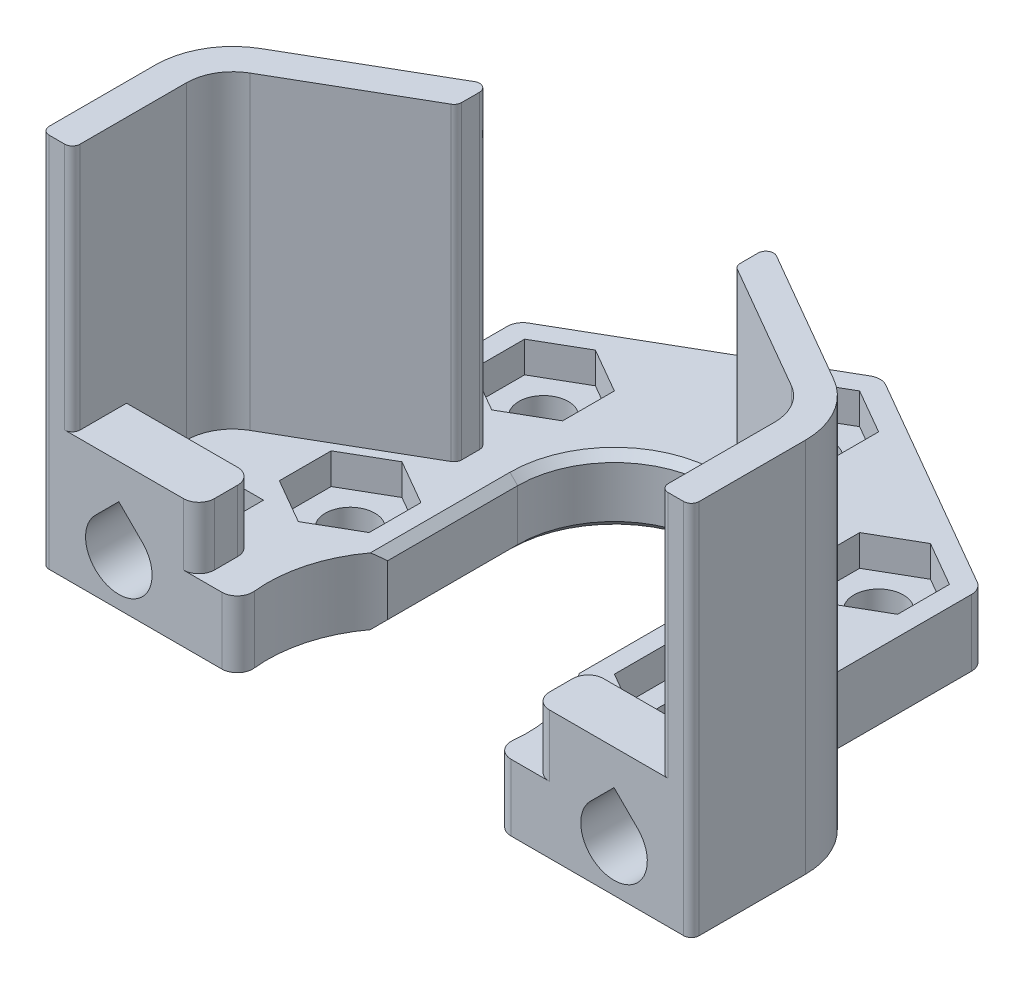
SolidWorks part; units mm, degrees
ref_plane "Front Plane" through (0, 0, 0) normal (0, 0, 1) x (1, 0, 0)
ref_plane "Top Plane" through (0, 0, 0) normal (0, 1, 0) x (1, 0, 0)
ref_plane "Right Plane" through (0, 0, 0) normal (1, 0, 0) x (0, 0, -1)
sketch "Sketch1" plane through (0, 0, 0) normal (0, 1, 0) x (1, 0, 0)
  line L0 (0, 0) -> (0, -54.0828) construction
  line L1 (0, 17.3205) -> (-15, 8.6603)
  line L2 (-15, 8.6603) -> (-15, -8.6603)
  line L3 (-15, -8.6603) -> (-6.25, -13.7121)
  line L4 (6.25, -13.7121) -> (15, -8.6603)
  line L5 (15, -8.6603) -> (15, 8.6603)
  line L6 (15, 8.6603) -> (0, 17.3205)
  line L7 (0, -54.6431) -> (0, 54.6431) construction
  line L8 (6.25, 0) -> (6.25, -13.7121)
  line L9 (-6.25, 0) -> (-6.25, -13.7121)
  line L11 (0, 12.5) -> (-10.8253, 6.25) construction
  line L12 (-10.8253, 6.25) -> (-10.8253, -6.25) construction
  line L13 (-10.8253, -6.25) -> (0, -12.5) construction
  line L14 (0, -12.5) -> (10.8253, -6.25) construction
  line L15 (10.8253, -6.25) -> (10.8253, 6.25) construction
  line L16 (10.8253, 6.25) -> (0, 12.5) construction
  circle A0 centre (0, 0) radius 15 construction
  arc A1 (6.25, 0) -> (-6.25, 0) centre (0, 0) ccw
  circle A2 centre (0, 0) radius 10.8253 construction
  circle A3 centre (0, 12.5) radius 1.6
  circle A4 centre (10.8253, 6.25) radius 1.6
  circle A5 centre (10.8253, -6.25) radius 1.6
  circle A6 centre (-10.8253, -6.25) radius 1.6
  circle A7 centre (-10.8253, 6.25) radius 1.6
  point P1 (0, -27.0414)
  dimension "D4" = 3.2
  dimension "D1" = 12.5
  dimension "D2" = 30
  dimension "D3" = 25
extrude "Boss-Extrude1" add sketch "Sketch1" along normal blind 4.3
fillet "Fillet1" radius 1 7 edges at (15, 2.15, -8.6603) (0, 2.15, -17.3205) (-15, 2.15, -8.6603) (-6.25, 2.15, 13.7121) (6.25, 2.15, 13.7121) (15, 2.15, 8.6603) (-15, 2.15, 8.6603)
sketch "Sketch2" plane through (0, 4.3, 0) normal (0, 1, 0) x (1, 0, 0)
  line L1 (0, 15.8486) -> (-2.9, 14.1743)
  line L2 (-2.9, 14.1743) -> (-2.9, 10.8257)
  line L3 (-2.9, 10.8257) -> (0, 9.1514)
  line L4 (0, 9.1514) -> (2.9, 10.8257)
  line L5 (2.9, 10.8257) -> (2.9, 14.1743)
  line L6 (2.9, 14.1743) -> (0, 15.8486)
  line L7 (13.7253, 4.5757) -> (13.7253, 7.9243)
  line L8 (13.7253, 7.9243) -> (10.8253, 9.5986)
  line L9 (10.8253, 9.5986) -> (7.9253, 7.9243)
  line L10 (7.9253, 7.9243) -> (7.9253, 4.5757)
  line L11 (7.9253, 4.5757) -> (10.8253, 2.9014)
  line L12 (10.8253, 2.9014) -> (13.7253, 4.5757)
  line L13 (13.7253, -4.5757) -> (10.8253, -2.9014)
  line L14 (10.8253, -2.9014) -> (7.9253, -4.5757)
  line L15 (7.9253, -4.5757) -> (7.9253, -7.9243)
  line L16 (7.9253, -7.9243) -> (10.8253, -9.5986)
  line L17 (10.8253, -9.5986) -> (13.7253, -7.9243)
  line L18 (13.7253, -7.9243) -> (13.7253, -4.5757)
  line L19 (-13.7253, -4.5757) -> (-13.7253, -7.9243)
  line L20 (-13.7253, -7.9243) -> (-10.8253, -9.5986)
  line L21 (-10.8253, -9.5986) -> (-7.9253, -7.9243)
  line L22 (-7.9253, -7.9243) -> (-7.9253, -4.5757)
  line L23 (-7.9253, -4.5757) -> (-10.8253, -2.9014)
  line L24 (-10.8253, -2.9014) -> (-13.7253, -4.5757)
  line L25 (-13.7253, 7.9243) -> (-13.7253, 4.5757)
  line L26 (-13.7253, 4.5757) -> (-10.8253, 2.9014)
  line L27 (-10.8253, 2.9014) -> (-7.9253, 4.5757)
  line L28 (-7.9253, 4.5757) -> (-7.9253, 7.9243)
  line L29 (-7.9253, 7.9243) -> (-10.8253, 9.5986)
  line L30 (-10.8253, 9.5986) -> (-13.7253, 7.9243)
  circle A0 centre (0, 12.5) radius 2.9 construction
  circle A1 centre (10.8253, 6.25) radius 2.9 construction
  circle A2 centre (10.8253, -6.25) radius 2.9 construction
  circle A3 centre (-10.8253, -6.25) radius 2.9 construction
  circle A4 centre (-10.8253, 6.25) radius 2.9 construction
  dimension "D1" = 5.8
extrude "Cut-Extrude1" cut sketch "Sketch2" against normal blind 2
sketch "Sketch3" plane through (0, 4.3, 0) normal (0, 1, 0) x (1, 0, 0)
  line L0 (0, 0) -> (0, -38.427) construction
  line L1 (-15, -8.0829) -> (-6.25, -11.98)
  line L2 (-20, -10.9697) -> (-20, -22.3767)
  line L3 (-18.3541, -24.0226) -> (18.3541, -24.0226)
  line L4 (20, -10.9697) -> (20, -22.3767)
  line L5 (0, -54.6431) -> (0, 54.6431) construction
  line L6 (15, -8.0829) -> (20, -10.9697)
  line L7 (-15, -8.0829) -> (-20, -10.9697)
  line L8 (-6.25, -11.98) -> (6.25, -11.98)
  line L9 (6.25, -11.98) -> (15, -8.0829)
  line L10 (-0.5, 17.0318) -> (-14.5, 8.9489) construction
  line L11 (14.5, 8.9489) -> (0.5, 17.0318) construction
  circle A0 centre (0, -14.0226) radius 10 construction
  arc A3 (20, -22.3767) -> (18.3541, -24.0226) centre (18.3541, -22.3767) cw
  arc A4 (-20, -22.3767) -> (-18.3541, -24.0226) centre (-18.3541, -22.3767) ccw
  point P31 (20, -24.0226)
  point P34 (-20, -24.0226)
  dimension "D1" = 20
  dimension "D2" = 40
extrude "Boss-Extrude2" add sketch "Sketch3" against normal up to surface (4.3 mm away) up to face at (-10.8253, 0, 7.85)
sketch "Sketch4" plane through (0, 4.3, 0) normal (0, 1, 0) x (1, 0, 0)
  line L0 (0, -54.6431) -> (0, 54.6431) construction
  circle A0 centre (0, -14.0226) radius 10 construction
  circle A1 centre (0, -14.0226) radius 8.4
  dimension "D1" = 20
  dimension "D2" = 16.8
extrude "Cut-Extrude2" cut sketch "Sketch4" against normal through all
sketch "Sketch5" plane through (0, 4.3, 0) normal (0, 1, 0) x (1, 0, 0)
  line L0 (-20, -10.9697) -> (-20, -22.3767) construction
  line L1 (-20, -16.0226) -> (20, -16.0226)
  line L2 (-20, -16.0226) -> (-20, -24.0226)
  line L3 (-20, -24.0226) -> (20, -24.0226)
  line L4 (20, -16.0226) -> (20, -24.0226)
  line L5 (-18.3541, -24.0226) -> (18.3541, -24.0226) construction
  line L6 (20, -22.3767) -> (20, -10.9697) construction
  point P0 (0, -16.0226)
  dimension "D1" = 8
extrude "Cut-Extrude3" cut sketch "Sketch5" against normal through all
other "Move Face1" face at (17.5, 2.15, 9.5263) face at (-17.5, 2.15, 9.5263) offset 5 parameters "D1"=5
sketch "Sketch6" plane through (0, 4.3, 0) normal (0, 1, 0) x (1, 0, 0)
  line L0 (-20, -12.5226) -> (-8.265, -12.5226)
  line L1 (8.265, -12.5226) -> (20, -12.5226)
  line L12 (8.1584, -16.0226) -> (20, -16.0226)
  line L13 (20, -16.0226) -> (20, -5.1962)
  line L14 (20, -5.1962) -> (15, -2.3094)
  line L15 (15, -2.3094) -> (15, 8.0829)
  line L16 (14.5, 8.9489) -> (0.5, 17.0318)
  line L17 (-0.5, 17.0318) -> (-14.5, 8.9489)
  line L18 (-15, 8.0829) -> (-15, -2.3094)
  line L19 (-15, -2.3094) -> (-20, -5.1962)
  line L20 (-20, -5.1962) -> (-20, -16.0226)
  line L21 (-20, -16.0226) -> (-8.1584, -16.0226)
  line L22 (-6.25, -8.4104) -> (-6.25, 0)
  line L23 (6.25, 0) -> (6.25, -8.4104)
  line L24 (8.1584, -16.0226) -> (20, -16.0226)
  line L25 (20, -16.0226) -> (20, -12.5226)
  line L32 (-20, -12.5226) -> (-20, -16.0226)
  line L33 (-20, -16.0226) -> (-8.1584, -16.0226)
  arc A6 (15, 8.0829) -> (14.5, 8.9489) centre (14, 8.0829) ccw
  arc A7 (0.5, 17.0318) -> (-0.5, 17.0318) centre (0, 16.1658) ccw
  arc A8 (-14.5, 8.9489) -> (-15, 8.0829) centre (-14, 8.0829) ccw
  arc A9 (-6.25, -8.4104) -> (-8.1584, -16.0226) centre (0, -14.0226) ccw
  arc A10 (6.25, 0) -> (-6.25, 0) centre (0, 0) ccw
  arc A11 (8.1584, -16.0226) -> (6.25, -8.4104) centre (0, -14.0226) ccw
  arc A15 (-8.265, -12.5226) -> (-8.1584, -16.0226) centre (0, -14.0226) ccw
  arc A17 (8.1584, -16.0226) -> (8.265, -12.5226) centre (0, -14.0226) ccw
  dimension "D2" = 3.5
  dimension "D1" = 0
extrude "Boss-Extrude3" add sketch "Sketch6" along normal blind 4
sketch "Sketch7" plane through (0, 0, 16.0226) normal (0, 0, 1) x (1, 0, 0)
  circle A0 centre (-16, 3) radius 2.15 construction
  circle A1 centre (-16, 3) radius 2.15
  circle A2 centre (16, 3) radius 2.15 construction
  circle A3 centre (16, 3) radius 2.15
extrude "Cut-Extrude4" cut sketch "Sketch7" against normal up to surface (3.5 mm away) up to face at (-14.1325, 6.3, 12.5226)
sketch "Sketch8" plane through (0, 0, 12.5226) normal (0, 0, -1) x (-1, 0, 0)
  line L0 (0, 0) -> (0, 29.9924) construction
  line L1 (16, 6.2909) -> (13.15, 4.6454)
  line L2 (13.15, 4.6454) -> (13.15, 1.3546)
  line L3 (13.15, 1.3546) -> (16, -0.2909)
  line L4 (16, -0.2909) -> (18.85, 1.3546)
  line L5 (18.85, 1.3546) -> (18.85, 4.6454)
  line L6 (18.85, 4.6454) -> (16, 6.2909)
  line L7 (0, 54.6431) -> (0, -54.6431) construction
  line L8 (-18.85, 4.6454) -> (-16, 6.2909)
  line L9 (-18.85, 1.3546) -> (-18.85, 4.6454)
  line L10 (-16, -0.2909) -> (-18.85, 1.3546)
  line L11 (-13.15, 1.3546) -> (-16, -0.2909)
  line L12 (-13.15, 4.6454) -> (-13.15, 1.3546)
  line L13 (-16, 6.2909) -> (-13.15, 4.6454)
  circle A0 centre (16, 3) radius 2.85 construction
  arc A1 (17.7125, 4.3) -> (14.2875, 4.3) centre (16, 3) ccw construction
  circle A2 centre (-16, 3) radius 2.85 construction
  dimension "D1" = 5.7
extrude "Cut-Extrude5" cut sketch "Sketch8" along normal blind 3
sketch "Sketch9" plane through (0, 4.3, 0) normal (0, 1, 0) x (1, 0, 0)
  line L0 (-8.265, -12.5226) -> (-13.15, -12.5226) construction
  line L1 (-10.8253, -12.5226) -> (10.8253, -12.5226)
  line L2 (-10.8253, -12.5226) -> (-10.8253, -16.0226)
  line L3 (-10.8253, -16.0226) -> (10.8253, -16.0226)
  line L4 (10.8253, -12.5226) -> (10.8253, -16.0226)
  line L5 (8.1584, -16.0226) -> (20, -16.0226) construction
extrude "Cut-Extrude6" cut sketch "Sketch9" along normal up to surface (4 mm away) up to face at (-14.152, 8.3, 14.274)
fillet "Fillet2" radius 1 12 edges at (15, 2.15, 2.3094) (20, 2.15, 5.1962) (20, 6.3, 12.5226) (-8.1584, 2.15, 16.0226) (8.1584, 2.15, 16.0226) (10.8253, 6.3, 16.0226) (10.8253, 6.3, 12.5226) (-10.8253, 6.3, 16.0226) (-10.8253, 6.3, 12.5226) (-20, 6.3, 12.5226) (-20, 2.15, 5.1962) (-15, 2.15, 2.3094)
chamfer "Chamfer1" distance 0.5 angle 45 6 edges at (-6.25, 4.3, 4.2052) (0, 4.3, -6.25) (6.25, 4.3, 4.2052) (6.25, 0, 4.2052) (0, 0, -6.25) (-6.25, 0, 4.2052)
sketch "Sketch10" plane through (0, 0, 16.0226) normal (0, 0, 1) x (1, 0, 0)
  line L0 (-17.5203, 4.5203) -> (-16, 6.0406)
  line L2 (-16, 6.0406) -> (-14.4797, 4.5203)
  line L3 (14.4797, 4.5203) -> (16, 6.0406)
  line L4 (16, 6.0406) -> (17.5203, 4.5203)
  circle A0 centre (-16, 3) radius 2.15 construction
  circle A1 centre (16, 3) radius 2.15 construction
  arc A2 (14.4797, 4.5203) -> (17.5203, 4.5203) centre (16, 3) ccw
  arc A3 (-17.5203, 4.5203) -> (-14.4797, 4.5203) centre (-16, 3) ccw
extrude "Cut-Extrude7" cut sketch "Sketch10" against normal up to surface (3.5 mm away) up to face at (18.15, 3, 12.5226)
sketch "Sketch11" plane through (0, 4.3, 0) normal (0, 1, 0) x (1, 0, 0)
  line L0 (9, -1.1547) -> (19, -6.9282)
  line L1 (19, -6.9282) -> (19, -16.0226)
  line L2 (11.8253, -16.0226) -> (20, -16.0226) construction
  line L3 (19, -16.0226) -> (21, -16.0226)
  line L4 (21, -16.0226) -> (21, -5.7735)
  line L5 (21, -5.7735) -> (9, 1.1547)
  line L6 (9, 1.1547) -> (9, -1.1547)
  line L7 (19.5, -4.9075) -> (15.5, -2.5981) construction
  line L8 (15, -1.7321) -> (15, 8.0829) construction
  line L9 (0, 0) -> (0, -19.4821) construction
  line L10 (0, -54.6431) -> (0, 54.6431) construction
  line L11 (-9, 1.1547) -> (-9, -1.1547)
  line L12 (-21, -5.7735) -> (-9, 1.1547)
  line L13 (-21, -16.0226) -> (-21, -5.7735)
  line L14 (-19, -16.0226) -> (-21, -16.0226)
  line L15 (-19, -6.9282) -> (-19, -16.0226)
  line L16 (-9, -1.1547) -> (-19, -6.9282)
  dimension "D1" = 2
  dimension "D2" = 6
  dimension "D3" = 2
extrude "Boss-Extrude4" add sketch "Sketch11" against normal up to surface (4.3 mm away) and the other way blind 20 up to face at (-10.8253, 0, -4.65)
fillet "Fillet3" radius 3 2 edges at (19, 14.3, 6.9282) (-19, 14.3, 6.9282)
fillet "Fillet4" radius 5 2 edges at (21, 12.15, 5.7735) (-21, 12.15, 5.7735)
fillet "Fillet5" radius 0.5 8 edges at (-9, 14.3, -1.1547) (-9, 14.3, 1.1547) (9, 14.3, -1.1547) (9, 14.3, 1.1547) (21, 12.15, 16.0226) (19, 16.3, 16.0226) (-19, 16.3, 16.0226) (-21, 12.15, 16.0226)
